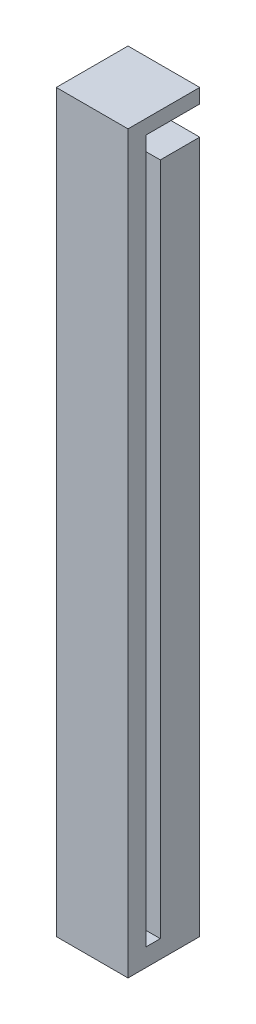
SolidWorks part; units mm, degrees
ref_plane "Front Plane" through (0, 0, 0) normal (0, 0, 1) x (1, 0, 0)
ref_plane "Top Plane" through (0, 0, 0) normal (0, 1, 0) x (1, 0, 0)
ref_plane "Right Plane" through (0, 0, 0) normal (1, 0, 0) x (0, 0, -1)
sketch "Sketch1" plane through (0, 0, 0) normal (0, 1, 0) x (1, 0, 0)
  line L1 (0, 0) -> (10, 0)
  line L2 (0, 0) -> (0, 10)
  line L3 (0, 10) -> (10, 10)
  line L4 (10, 0) -> (10, 10)
  dimension "D1" = 10
extrude "Boss-Extrude1" add sketch "Sketch1" along normal blind 100
sketch "Sketch3" plane through (0, 0, -10) normal (0, 0, -1) x (-1, 0, 0)
  line L0 (-10, 100) -> (-10, 0) construction
  line L1 (-2.5, 98) -> (-10, 98)
  line L2 (-2.5, 98) -> (-2.5, 94)
  line L3 (-2.5, 94) -> (-10, 94)
  line L4 (-10, 98) -> (-10, 94)
  line L5 (-10, 100) -> (0, 100) construction
  line L6 (0, 100) -> (0, 0) construction
  dimension "D1" = 2
  dimension "D2" = 4
  dimension "D3" = 2.5
extrude "Cut-Extrude1" cut sketch "Sketch3" against normal offset from surface (7.5 mm away) 2.5 up to face at (5, 50, 0)
sketch "Sketch4" plane through (0, 0, 0) normal (0, -1, 0) x (1, 0, 0)
  line L0 (2.5, -2.5) -> (2.5, -10) construction
  line L1 (2.5, -2.5) -> (2.5, -10)
  line L2 (2.5, -2.5) -> (10, -2.5) construction
  line L3 (2.5, -2.5) -> (10, -2.5)
  line L4 (10, -10) -> (0, -10) construction
  line L5 (10, -2.5) -> (2.5, -2.5)
  line L6 (10, -2.5) -> (10, -4.5)
  line L7 (10, -4.5) -> (2.5, -4.5)
  line L8 (2.5, -2.5) -> (2.5, -4.5)
  line L9 (4.5, -10) -> (2.5, -10)
  line L10 (4.5, -10) -> (4.5, -4.5)
  line L11 (4.5, -4.5) -> (2.5, -4.5)
  line L12 (2.5, -10) -> (2.5, -4.5)
  line M10 (0, -10) -> (10, -10)
  line M11 (10, -10) -> (10, 0)
  dimension "D1" = 2
  dimension "D2" = 2
extrude "Cut-Extrude2" cut sketch "Sketch4" against normal up to surface (98 mm away) contours L7 L3 L1 M11 | L10 L7 L1 M10 region at (6.25, 0, -3.5) region at (3.5, 0, -7.25) up to face at (6.25, 98, -6.25)
sketch "Sketch5" plane through (0, 0, 0) normal (0, -1, 0) x (1, 0, 0)
  line L1 (0, 0) -> (10, 0)
  line L2 (0, 0) -> (0, -10)
  line L3 (0, -10) -> (10, -10)
  line L4 (10, 0) -> (10, -10)
extrude "Boss-Extrude2" add sketch "Sketch5" along normal blind 2.5
sketch "Sketch6" plane through (0, 0, 0) normal (0, 1, 0) x (1, 0, 0)
  line L0 (10, 4.5) -> (4.5, 4.5) construction
  line L1 (2.5, 2.5) -> (6.5, 2.5)
  line L2 (2.5, 2.5) -> (2.5, 4.5)
  line L3 (2.5, 4.5) -> (6.5, 4.5)
  line L4 (6.5, 2.5) -> (6.5, 4.5)
  line L5 (4.5, 10) -> (4.5, 4.5) construction
  line L6 (2.5, 4.5) -> (4.5, 4.5)
  line L7 (2.5, 4.5) -> (2.5, 6.5)
  line L8 (2.5, 6.5) -> (4.5, 6.5)
  line L9 (4.5, 4.5) -> (4.5, 6.5)
  line L10 (3.5, 2.5) -> (3.5, 6.5) construction
  line M7 (10, 4.5) -> (4.5, 4.5)
  line M8 (4.5, 4.5) -> (4.5, 10)
  line M10 (2.5, 10) -> (2.5, 2.5)
  line M11 (2.5, 2.5) -> (10, 2.5)
  dimension "D1" = 4
extrude "Boss-Extrude3" add sketch "Sketch6" along normal up to surface (98 mm away) contours L10 L1 L4 L6 M7 | L10 L6 L8 M8 | L3 L10 L8 M10 | L10 L3 M11 M10 region at (3, 0, -3.5) region at (5, 0, -3.5) region at (3, 0, -5.5) region at (4, 0, -5.5) up to face at (6.25, 98, -6.25)
